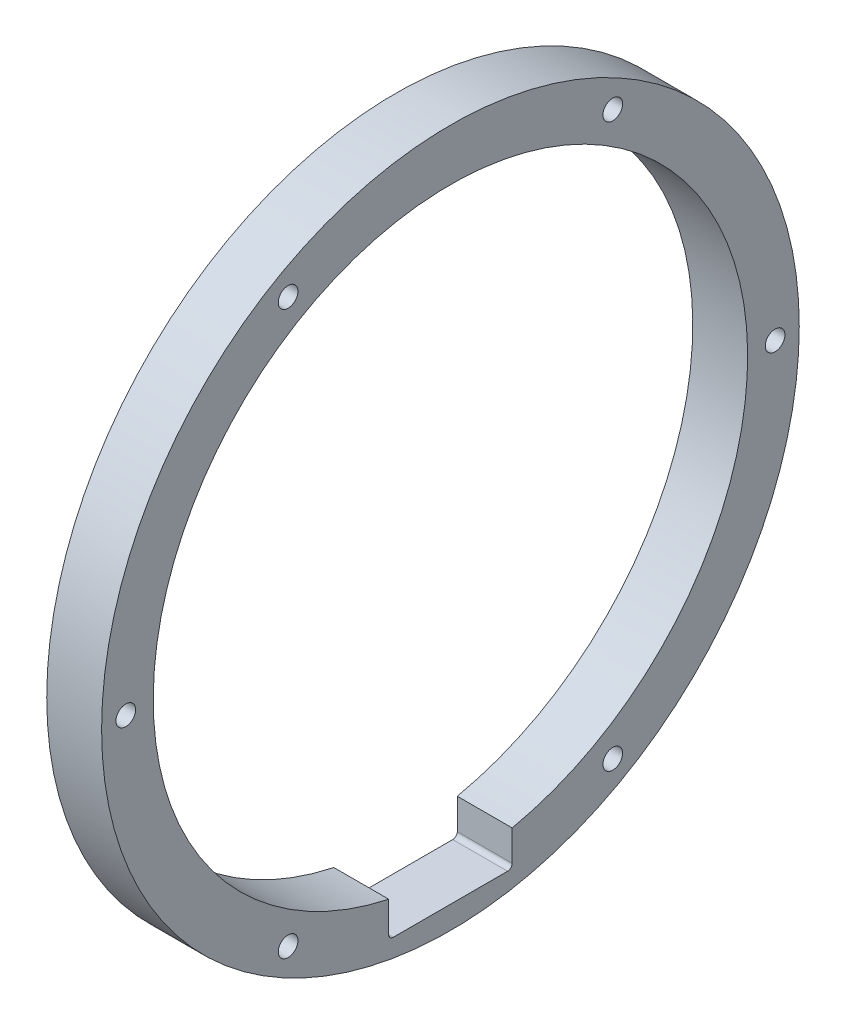
SolidWorks part; units mm, degrees
ref_plane "Front Plane" through (0, 0, 0) normal (0, 0, 1) x (1, 0, 0)
ref_plane "Top Plane" through (0, 0, 0) normal (0, 1, 0) x (1, 0, 0)
ref_plane "Right Plane" through (0, 0, 0) normal (1, 0, 0) x (0, 0, -1)
sketch "Sketch1" plane through (0, 0, 0) normal (1, 0, 0) x (0, 0, -1)
  circle A0 centre (0, 0) radius 76.29
  circle A1 centre (0, 0) radius 65
  dimension "D1" = 152.58
  dimension "D2" = 130
extrude "Boss-Extrude1" add sketch "Sketch1" along normal blind 12
sketch "Sketch2" plane through (12, 0, 0) normal (1, 0, 0) x (0, 0, -1)
  line L0 (0, -34.8517) -> (0, -97.703) construction
  line L1 (-13.5, -51.894) -> (13.5, -51.894)
  line L2 (-13.5, -51.894) -> (-13.5, -70.29)
  line L3 (-12.5, -71.29) -> (12.5, -71.29)
  line L4 (13.5, -51.894) -> (13.5, -70.29)
  circle A1 centre (0, 0) radius 76.29 construction
  arc A2 (-13.5, -70.29) -> (-12.5, -71.29) centre (-12.5, -70.29) ccw
  arc A3 (13.5, -70.29) -> (12.5, -71.29) centre (12.5, -70.29) cw
  point P6 (0, -51.894)
  point P7 (0, -78.4285)
  point P10 (0, -76.29)
  point P12 (0, 0)
  point P13 (0, 0)
  dimension "D2" = 1
  dimension "D3" = 1
  dimension "D1" = 5
  dimension "D4" = 27
extrude "Cut-Extrude1" cut sketch "Sketch2" against normal up to next
sketch "Sketch3" plane through (12, 0, 0) normal (1, 0, 0) x (0, 0, -1)
  line L0 (-94.7404, 0) -> (95.285, 0) construction
  circle A0 centre (-71, 0) radius 2.15
  circle A1 centre (-35.5, 61.4878) radius 2.15
  circle A2 centre (35.5, 61.4878) radius 2.15
  circle A3 centre (71, 0) radius 2.15
  circle A4 centre (35.5, -61.4878) radius 2.15
  circle A5 centre (-35.5, -61.4878) radius 2.15
  point P17 (0, 0)
  dimension "D1" = 4.3
  dimension "D2" = 71
  dimension "D3" = 6
extrude "Cut-Extrude2" cut sketch "Sketch3" against normal up to next
